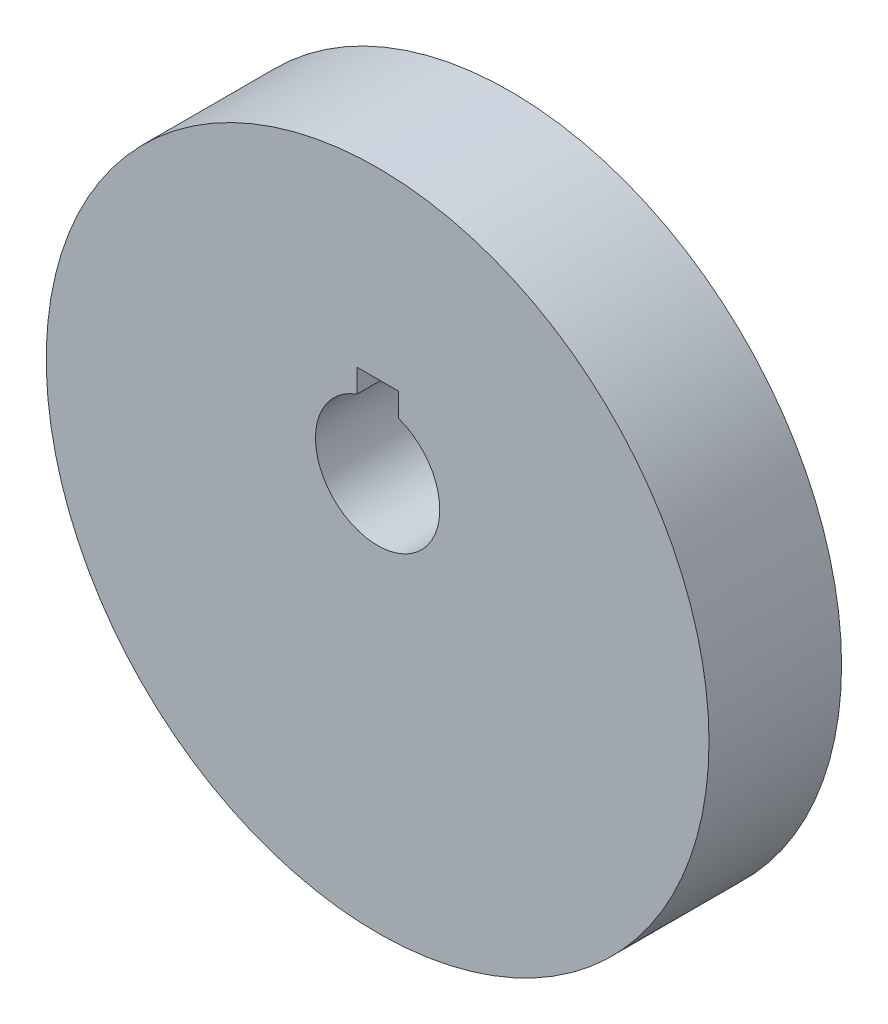
SolidWorks part; units mm, degrees
material "Brass"
ref_plane "Front Plane" through (0, 0, 0) normal (0, 0, 1) x (1, 0, 0)
ref_plane "Top Plane" through (0, 0, 0) normal (0, 1, 0) x (1, 0, 0)
ref_plane "Right Plane" through (0, 0, 0) normal (1, 0, 0) x (0, 0, -1)
sketch "Sketch1" plane through (0, 0, 0) normal (0, 0, 1) x (1, 0, 0)
  circle A0 centre (0, -5.08) radius 25.4
  dimension "D2" = 50.8
  dimension "D1" = 5.08
extrude "Boss-Extrude1" add sketch "Sketch1" along normal blind 10.16
sketch "Sketch2" plane through (0, 0, 0) normal (0, 0, 1) x (1, 0, 0)
  circle A0 centre (0, 0) radius 4.7625
  dimension "D1" = 9.525
extrude "Cut-Extrude2" cut sketch "Sketch2" against normal blind 12.16 and the other way blind 12.16
sketch "Sketch3" plane through (0, 0, 0) normal (0, 0, 1) x (1, 0, 0)
  line L0 (-1.5875, 2.3812) -> (1.5875, 2.3812)
  line L1 (1.5875, 2.3812) -> (1.5875, 6.2865)
  line L2 (1.5875, 6.2865) -> (-1.5875, 6.2865)
  line L3 (-1.5875, 6.2865) -> (-1.5875, 2.3812)
  dimension "D1" = 3.175
  dimension "D2" = 3.9052
  dimension "D3" = 1.5875
  dimension "D4" = 2.3812
extrude "Cut-Extrude4" cut sketch "Sketch3" against normal blind 12.16 and the other way blind 12.16
